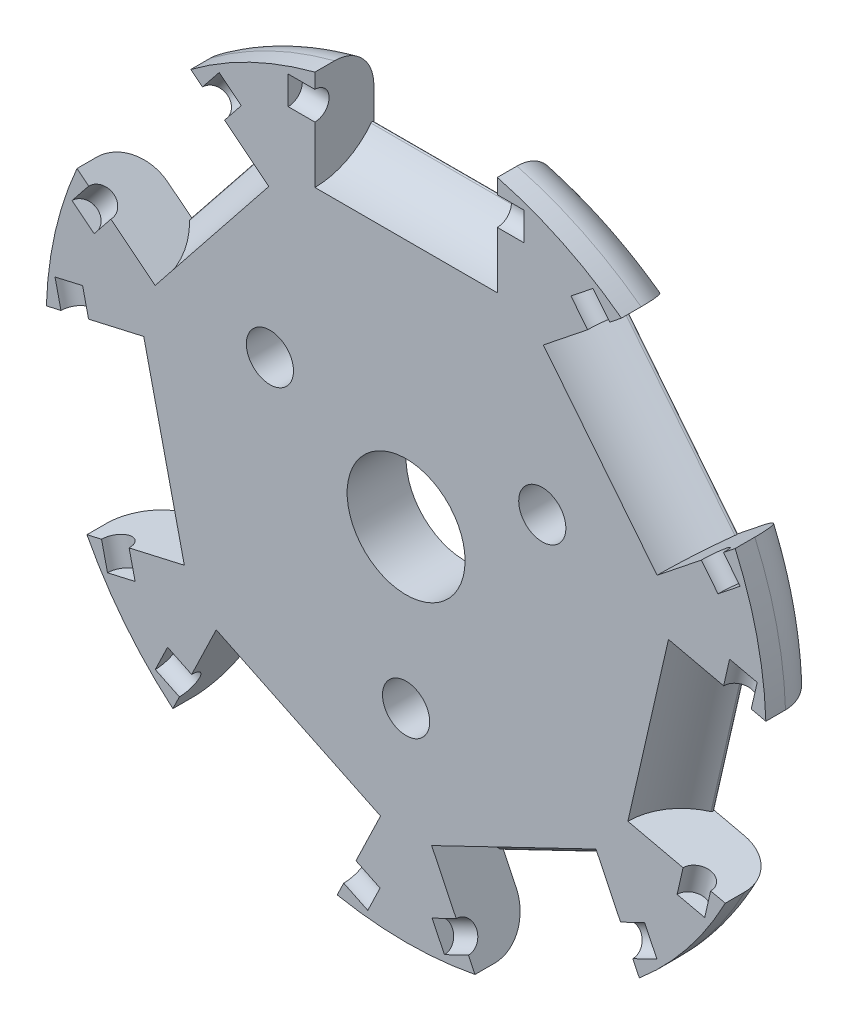
SolidWorks part; units mm, degrees
other "Markup1"
sketch "Sketch8" plane through (32.7336, 32.7336, 0) normal (0.5701, 0.1846, 0.8006) x (0.8043, 0.0736, -0.5897)
ref_plane "Front Plane" through (0, 0, 0) normal (0, 0, 1) x (1, 0, 0)
ref_plane "Top Plane" through (0, 0, 0) normal (0, 1, 0) x (1, 0, 0)
ref_plane "Right Plane" through (0, 0, 0) normal (1, 0, 0) x (0, 0, -1)
sketch "Sketch1" plane through (0, 0, 0) normal (0, 0, 1) x (1, 0, 0)
  circle A0 centre (0, 0) radius 29.0703
  dimension "D1" = 58.1406
extrude "Boss-Extrude2" add sketch "Sketch1" against normal blind 4.7625
fillet "Fillet1" radius 3.175 1 edges at (29.0703, 0, -4.7625)
sketch "Sketch2" plane through (0, 0, 0) normal (0, 0, 1) x (1, 0, 0)
  line L1 (-12.7, 29.0703) -> (12.7, 29.0703) construction
  line L2 (-7.366, 30.3403) -> (7.366, 30.3403)
  line L3 (-7.366, 30.3403) -> (-7.366, 19.9263)
  line L4 (-7.366, 19.9263) -> (7.366, 19.9263)
  line L5 (7.366, 30.3403) -> (7.366, 19.9263)
  line L6 (-7.366, 30.3403) -> (7.366, 19.9263) construction
  line L7 (-7.366, 19.9263) -> (7.366, 30.3403) construction
  line L35 (0, 0) -> (0, 29.0703) construction
  circle A1 centre (0, 0) radius 29.0703 construction
  point P10 (0, 25.1333)
  circle M7 centre (0, 0) radius 29.0703
  dimension "D1" = 14.732
  dimension "D2" = 10.414
  dimension "D3" = 1.27
  dimension "D4" = 25.4
extrude "Cut-Extrude2" cut sketch "Sketch2" against normal blind 12.7 contours L5 L3 L4 M7 | L3 L2 L5 L4 region at (0, 24.3457, 0)
pattern_circular "CirPattern1" count 7 over 360 about axis through (0, 0, 0) along (0, 0, 1) of "Cut-Extrude2"
ref_plane "Plane1" through (0, 0, 0) normal (1, 0, 0) x (0, 0, -1)
sketch "Sketch4" plane through (0, 0, 0) normal (1, 0, 0) x (0, 0, -1)
  line L0 (4.7625, 19.9263) -> (0, 19.9263) construction
  circle A0 centre (0, 25.7683) radius 1.143
  dimension "D1" = 2.286
  dimension "D2" = 5.842
extrude "Cut-Extrude4" cut sketch "Sketch4" against normal mid plane 19.05
pattern_circular "CirPattern2" count 7 over 360 about axis through (0, 0, 0) along (0, 0, 1) of "Cut-Extrude4"
sketch "Sketch5" plane through (0, 0, 0) normal (0, 0, 1) x (1, 0, 0)
  circle A0 centre (0, 0) radius 4.7625
  dimension "D1" = 9.525
sketch "Sketch6" plane through (0, 0, -4.7625) normal (0, 0, -1) x (-1, 0, 0)
  circle A1 centre (0, -12.7) radius 1.905
  circle A4 centre (-10.9985, 6.35) radius 1.905
  circle A5 centre (10.9985, 6.35) radius 1.905
  point P0 (0, 0)
  point P12 (0, 0)
  dimension "D4" = 3.81
  dimension "D1" = 12.7
  dimension "D2" = 3
extrude "Cut-Extrude7" cut sketch "Sketch6" against normal through all
sketch "Sketch10" plane through (7.366, 0, 0) normal (-1, 0, 0) x (0, 0, 1)
  line L0 (-4.7625, 24.8256) -> (-4.7625, 19.9263) construction
  line L1 (-4.7625, 19.9263) -> (0, 19.9263)
  line L2 (-4.7625, 19.9263) -> (-4.7625, 22.6092)
  line L4 (0, 19.9263) -> (0, 20.0533)
  arc A0 (-4.7625, 22.6092) -> (0, 20.0533) centre (0, 25.7683) ccw
  dimension "D1" = 11.43
  dimension "D2" = 4.7625
extrude "Boss-Extrude4" add sketch "Sketch10" along normal up to next
fillet "Fillet2" radius 0.127 1 edges at (0, 22.6092, -4.7625)
pattern_circular "CirPattern5" count 7 over 360 about axis through (0, 0, 0) along (0, 0, 1) of "Boss-Extrude4", "Fillet2"
extrude "Cut-Extrude9" cut sketch "Sketch5" against normal up to next
